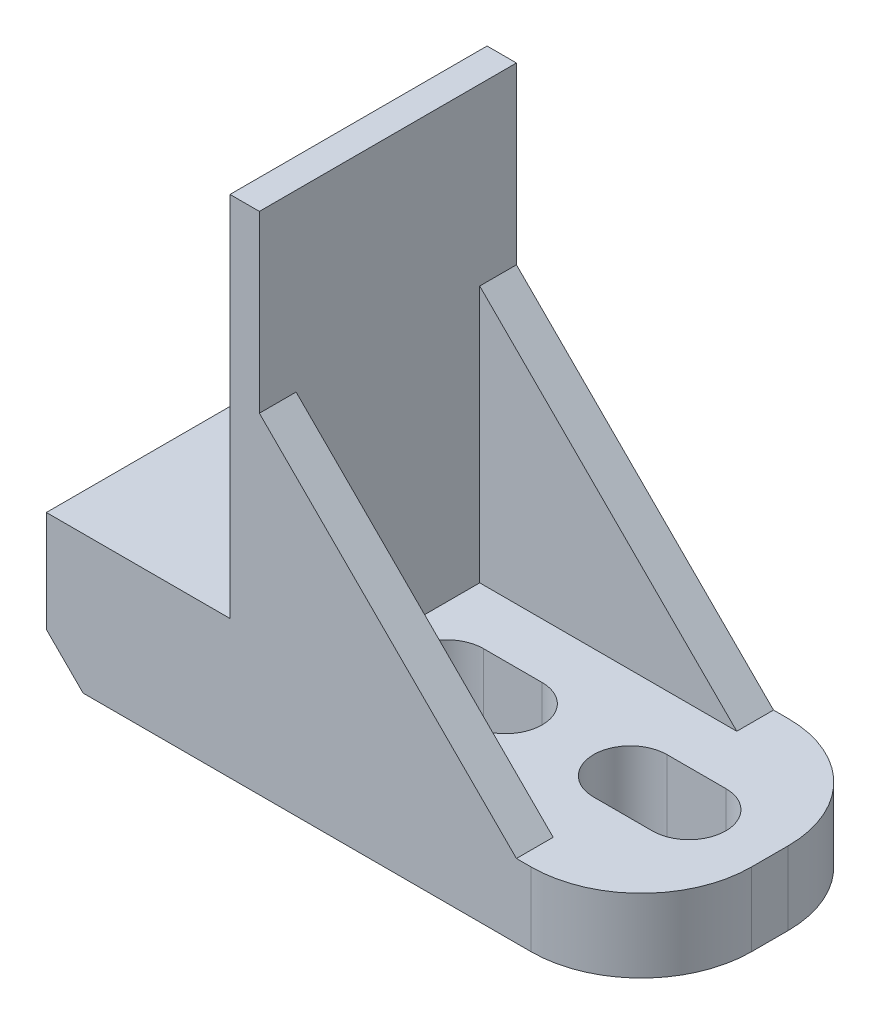
SolidWorks part; units mm, degrees
ref_plane "Front Plane" through (0, 0, 0) normal (0, 0, 1) x (1, 0, 0)
ref_plane "Top Plane" through (0, 0, 0) normal (0, 1, 0) x (1, 0, 0)
ref_plane "Right Plane" through (0, 0, 0) normal (1, 0, 0) x (0, 0, -1)
sketch "Sketch1" plane through (0, 0, 0) normal (0, 0, 1) x (1, 0, 0)
  line L0 (-41.5405, -20.2324) -> (-122.5405, -20.2324)
  line L1 (-122.5405, -20.2324) -> (-122.5405, -1.4324)
  line L2 (-122.5405, -1.4324) -> (-97.5405, -1.4324)
  line L3 (-97.5405, -1.4324) -> (-97.5405, 48.5676)
  line L4 (-97.5405, 48.5676) -> (-93.5405, 48.5676)
  line L5 (-93.5405, 48.5676) -> (-93.5405, -10.2324)
  line L6 (-93.5405, -10.2324) -> (-41.5405, -10.2324)
  line L7 (-41.5405, -10.2324) -> (-41.5405, -20.2324)
  dimension "D1" = 4
  dimension "D2" = 18.8
  dimension "D3" = 25
  dimension "D4" = 52
  dimension "D5" = 50
  dimension "D6" = 10
extrude "Boss-Extrude1" add sketch "Sketch1" along normal blind 35
ref_plane "Plane1" through (0, 0, 17.5) normal (0, 0, -1) x (-1, 0, 0)
sketch "Sketch2" plane through (0, 0, 0) normal (0, 1, 0) x (1, 0, 0)
  line L0 (-85.5405, -17.5) -> (-77.5405, -17.5) construction
  line L1 (-85.5405, -12.5) -> (-77.5405, -12.5)
  line L2 (-85.5405, -22.5) -> (-77.5405, -22.5)
  line L3 (-60.5405, -17.5) -> (-52.5405, -17.5) construction
  line L4 (-60.5405, -12.5) -> (-52.5405, -12.5)
  line L5 (-60.5405, -22.5) -> (-52.5405, -22.5)
  line L6 (37.84, -17.5) -> (-37.84, -17.5) construction
  line L7 (-97.5405, -35) -> (-97.5405, 0) construction
  arc A0 (-85.5405, -12.5) -> (-85.5405, -22.5) centre (-85.5405, -17.5) ccw
  arc A1 (-77.5405, -22.5) -> (-77.5405, -12.5) centre (-77.5405, -17.5) ccw
  arc A2 (-60.5405, -12.5) -> (-60.5405, -22.5) centre (-60.5405, -17.5) ccw
  arc A3 (-52.5405, -22.5) -> (-52.5405, -12.5) centre (-52.5405, -17.5) ccw
  point P2 (-81.5405, -17.5)
  point P9 (-56.5405, -17.5)
  dimension "D1" = 5
  dimension "D3" = 5
  dimension "D2" = 8
  dimension "D4" = 8
  dimension "D5" = 16
  dimension "D6" = 25
sketch "Sketch3" plane through (0, 0, 0) normal (0, 0, 1) x (1, 0, 0)
  line L0 (-93.5405, 24.7676) -> (-93.5405, -10.2324)
  line L1 (-93.5405, -10.2324) -> (-58.5405, -10.2324)
  line L2 (-58.5405, -10.2324) -> (-93.5405, 24.7676)
  line L3 (-93.5405, -10.2324) -> (-93.5405, 48.5676) construction
  line L4 (-41.5405, -10.2324) -> (-93.5405, -10.2324) construction
  dimension "D1" = 35
extrude "Boss-Extrude2" add sketch "Sketch3" along normal blind 5
extrude "Boss-Extrude3" add sketch "Sketch3<2>" against normal blind 5 from surface starting at face at (-88.7905, 4.1676, 35)
sketch "Sketch3<2>" plane through (0, 0, 0) normal (0, 0, 1) x (1, 0, 0) same geometry as "Sketch3"
extrude "Cut-Extrude1" cut sketch "Sketch2" against normal through all
chamfer "Chamfer1" distance 5 angle 45 1 edges at (-122.5405, -20.2324, 17.5)
fillet "Fillet1" radius 15 2 edges at (-41.5405, -15.2324, 0) (-41.5405, -15.2324, 35)
